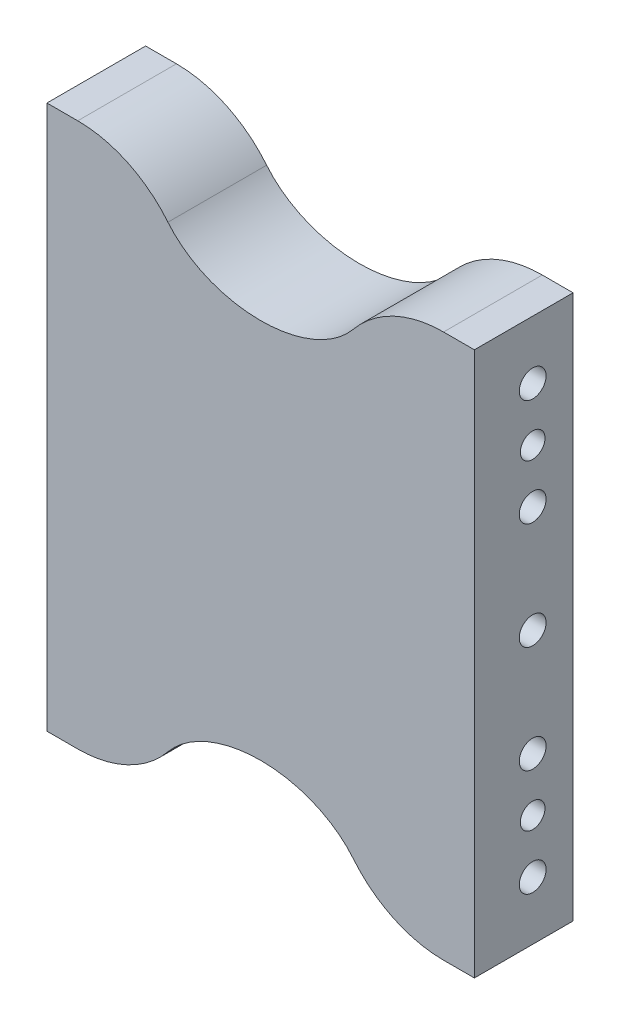
SolidWorks part; units mm, degrees
material "AISI 316 Annealed Stainless Steel Bar (SS)"
ref_plane "Front" through (0, 0, 0) normal (0, 0, 1) x (1, 0, 0)
ref_plane "Top" through (0, 0, 0) normal (0, 1, 0) x (1, 0, 0)
ref_plane "Right" through (0, 0, 0) normal (1, 0, 0) x (0, 0, -1)
sketch "Sketch1" plane through (0, 0, 0) normal (0, 0, 1) x (1, 0, 0)
  line L0 (-27.5, 0) -> (27.5, 0) construction
  line L1 (-27.5, -35) -> (27.5, -35)
  line L2 (-27.5, -35) -> (-27.5, 35)
  line L3 (-27.5, 35) -> (27.5, 35)
  line L4 (27.5, -35) -> (27.5, 35)
  dimension "D1" = 70
  dimension "D2" = 55
extrude "Boss-Extrude1" add sketch "Sketch1" along normal blind 12.7
sketch "Sketch21" plane through (0, 0, 12.7) normal (0, 0, 1) x (1, 0, 0)
  line L0 (27.5, 35) -> (-27.5, 35) construction
  line L1 (-27.5, -35) -> (27.5, -35) construction
  circle A0 centre (0, 35) radius 10.5 construction
  circle A1 centre (0, -35) radius 10.5 construction
  ellipse E0 centre (0, 35) end of major axis (14, 35) minor radius 10.5
  ellipse E1 centre (0, -35) end of major axis (14, -35) minor radius 10.5
  dimension "D1" = 21
  dimension "D2" = 28
extrude "Cut-Extrude1" cut sketch "Sketch21" against normal through all
fillet "Fillet2" radius 15 4 edges at (-14, 35, 6.35) (14, 35, 6.35) (14, -35, 6.35) (-14, -35, 6.35)
fillet "Fillet1" [suppressed] radius 5 profile chamfer
hole_wizard "#8-32 Tapped Hole1" positions "Sketch15" profile "Sketch16" tap size "#8-32" standard "ANSI Inch"
sketch "Sketch15" plane through (27.5, 0, 0) normal (1, 0, 0) x (0, 0, -1)
  line L0 (-12.7, 0) -> (-5.2, 0) construction
  line L2 (-5.2, 0) -> (-5.2, 13.75) construction
  line L3 (-5.2, 13.75) -> (-5.2, 27.5) construction
  line L6 (-5.2, -27.5) -> (-5.2, -13.75) construction
  line L7 (-5.2, -13.75) -> (-5.2, 0) construction
  line L8 (-5.2, 0) -> (0, 0) construction
  line L10 (-12.7, -35) -> (-12.7, 35) construction
  line L12 (0, -35) -> (0, 35) construction
  point P0 (-5.2, -27.5)
  point P3 (-5.2, -13.75)
  point P6 (-5.2, 0)
  point P9 (-5.2, 27.5)
  point P12 (-5.2, 13.75)
  dimension "D1" = 7.5
  dimension "D2" = 13.75
sketch "Sketch16" plane through (27.5, -27.5, 5.2) normal (0, 1, 0) x (0, 0, -1)
  line L0 (0, 0) -> (0, 11.7478)
  line L1 (0, 11.7478) -> (1.7272, 10.71)
  line L2 (1.7272, 10.71) -> (1.7272, 0)
  line L5 (1.7272, 0) -> (0, 0)
  line L10 (0, 11.7478) -> (-1.7272, 10.71) construction
  line L11 (0, -6.35) -> (0, 107.95) construction
  dimension "Tap Drill Dia." = 3.4544
  dimension "Tap Drill Depth" = 10.71
  dimension "Drill Angle" = 118
cosmetic thread "Hole Thread5" parameters "D1"=8.33, "D2"=4.1656
cosmetic thread "Hole Thread6" parameters "D1"=8.33, "D2"=4.1656
cosmetic thread "Hole Thread7" parameters "D1"=8.33, "D2"=4.1656
cosmetic thread "Hole Thread8" parameters "D1"=8.33, "D2"=4.1656
cosmetic thread "Hole Thread9" parameters "D1"=8.33, "D2"=4.1656
hole_wizard "1/8 (0.1250) Dowel Hole1" positions "Sketch19" profile "Sketch20" hole size "1/8" standard "ANSI Inch"
sketch "Sketch19" plane through (27.5, 0, 0) normal (1, 0, 0) x (0, 0, -1)
  line L0 (-5.2, -27.5) -> (-5.2, -13.75) construction
  line L3 (-5.2, 13.75) -> (-5.2, 27.5) construction
  point P0 (-5.2, -20.625)
  point P2 (-5.2, 20.625)
sketch "Sketch20" plane through (27.5, -20.625, 5.2) normal (0, 1, 0) x (0, 0, -1)
  line L0 (0, 0) -> (0, 4.9539)
  line L1 (0, 4.9539) -> (1.5875, 4)
  line L2 (1.5875, 4) -> (1.5875, 0)
  line L5 (1.5875, 0) -> (0, 0)
  line L10 (0, 4.9539) -> (-1.5875, 4) construction
  line L11 (0, -6.35) -> (0, 107.95) construction
  dimension "Hole Dia." = 3.175
  dimension "Hole Depth" = 4
  dimension "Drill Angle" = 118
mirror "Mirror1" about plane through (0, 0, 0) normal (1, 0, 0) of "1/8 (0.1250) Dowel Hole1", "#8-32 Tapped Hole1"
